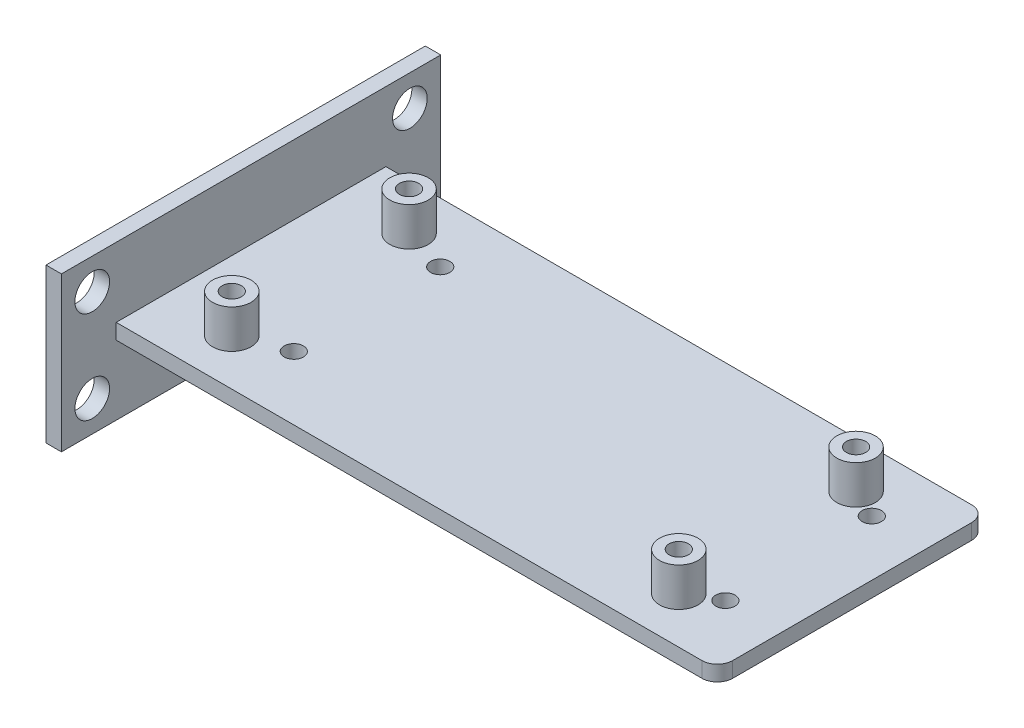
SolidWorks part; units mm, degrees
material "ABS"
ref_plane "Спереди" through (0, 0, 0) normal (0, 0, 1) x (1, 0, 0)
ref_plane "Сверху" through (0, 0, 0) normal (0, 1, 0) x (1, 0, 0)
ref_plane "Справа" through (0, 0, 0) normal (1, 0, 0) x (0, 0, -1)
sketch "Эскиз1" plane through (0, 0, 0) normal (0, 1, 0) x (1, 0, 0)
  line L1 (0, 0) -> (80, 0)
  line L2 (0, 0) -> (0, -35)
  line L3 (0, -35) -> (80, -35)
  line L4 (80, 0) -> (80, -35)
  dimension "D1" = 80
  dimension "D2" = 35
extrude "Бобышка-Вытянуть1" add sketch "Эскиз1" along normal blind 2
sketch "Эскиз2" plane through (0, 2, 0) normal (0, 1, 0) x (1, 0, 0)
  line L0 (0, 0) -> (0, -35) construction
  line L1 (80, -35) -> (80, 0) construction
  line L2 (80, 0) -> (0, 0) construction
  line L3 (0, -35) -> (80, -35) construction
  circle A0 centre (11, -6) radius 2.5
  circle A1 centre (11, -29) radius 2.5
  circle A2 centre (69, -6) radius 2.5
  circle A3 centre (69, -29) radius 2.5
  dimension "D1" = 11
  dimension "D2" = 11
  dimension "D3" = 11
  dimension "D4" = 11
  dimension "D5" = 6
  dimension "D6" = 6
  dimension "D7" = 5
  dimension "D8" = 6
  dimension "D9" = 6
  dimension "D10" = 5
  dimension "D11" = 5
  dimension "D12" = 5
extrude "Бобышка-Вытянуть2" add sketch "Эскиз2" along normal blind 5
sketch "Эскиз3" plane through (0, 7, 0) normal (0, 1, 0) x (1, 0, 0)
  circle A0 centre (11, -6) radius 1.25
  circle A1 centre (11, -29) radius 1.25
  circle A2 centre (69, -6) radius 1.25
  circle A3 centre (69, -29) radius 1.25
  dimension "D1" = 2.5
  dimension "D2" = 2.5
  dimension "D3" = 2.5
  dimension "D4" = 2.5
extrude "Вырез-Вытянуть1" cut sketch "Эскиз3" against normal through all both and the other way through all
sketch "Эскиз4" plane through (0, 2, 0) normal (0, 1, 0) x (1, 0, 0)
  line L0 (0, -17.5) -> (80, -17.5) construction
  line L1 (0, 0) -> (0, -35) construction
  line L2 (80, -35) -> (80, 0) construction
  circle A0 centre (4, -17.5) radius 2
  circle A1 centre (76, -17.5) radius 2
  dimension "D2" = 4
  dimension "D3" = 4
  dimension "D4" = 4
  dimension "D1" = 4
extrude "Вырез-Вытянуть2" [suppressed] cut sketch "Эскиз4" against normal through all
fillet "Скругление1" radius 2 1 edges at (0, 1, 0) type face fillet first side face at (0, 1, 17.5) second side face at (40, 1, 0)
fillet "Скругление2" radius 2 1 edges at (0, 1, 35) type face fillet first side face at (0, 1, 18.5) second side face at (40, 1, 35)
fillet "Скругление3" radius 2 1 edges at (80, 1, 35) type face fillet first side face at (41, 1, 35) second side face at (80, 1, 17.5)
fillet "Скругление4" radius 2 1 edges at (80, 1, 0) type face fillet first side face at (41, 1, 0) second side face at (80, 1, 16.5)
sketch "Эскиз5" plane through (0, 0, 0) normal (0, -1, 0) x (1, 0, 0)
  circle A0 centre (16.7893, 26.746) radius 1.25
  circle A1 centre (72.7893, 26.746) radius 1.25
  circle A2 centre (72.7893, 7.746) radius 1.25
  circle A3 centre (16.7893, 7.746) radius 1.25
  dimension "D1" = 2
  dimension "D2" = 2
extrude "Вырез-Вытянуть3" cut sketch "Эскиз5" against normal blind 10
sketch "Эскиз6" plane through (0, 0, 0) normal (0, -1, 0) x (1, 0, 0)
  circle A0 centre (16.7893, 26.746) radius 1.25
  circle A1 centre (16.7893, 26.746) radius 2.5
  circle A2 centre (72.7893, 26.746) radius 2.5
  circle A3 centre (72.7893, 26.746) radius 1.25
  circle A4 centre (72.7893, 7.746) radius 2.5
  circle A5 centre (72.7893, 7.746) radius 1.25
  circle A6 centre (16.7893, 7.746) radius 2.5
  circle A7 centre (16.7893, 7.746) radius 1.25
  dimension "D1" = 2
  dimension "D2" = 2
extrude "Бобышка-Вытянуть3" add sketch "Эскиз6" along normal blind 4
sketch "Эскиз7" plane through (0, 0, 0) normal (-1, 0, 0) x (0, 0, 1)
  line L0 (17.5, 2) -> (17.5, 0) construction
  line L1 (2, 2) -> (33, 2) construction
  line L2 (2, 0) -> (33, 0) construction
  line L3 (-7.1094, 1) -> (42.7824, 1) construction
  line L4 (42.1094, -9) -> (-7.1094, -9)
  line L5 (42.1094, -9) -> (42.1094, 11)
  line L6 (42.1094, 11) -> (-7.1094, 11)
  line L7 (-7.1094, -9) -> (-7.1094, 11)
  line L8 (42.1094, -9) -> (-7.1094, 11) construction
  line L9 (42.1094, 11) -> (-7.1094, -9) construction
  circle A0 centre (38.1094, -5) radius 2.25
  circle A1 centre (-3.1094, -5) radius 2.25
  circle A2 centre (-3.1094, 7) radius 2.25
  circle A3 centre (38.1094, 7) radius 2.25
  point P6 (17.5, 1)
  dimension "D1" = 4
  dimension "D2" = 4
  dimension "D3" = 20
extrude "Бобышка-Вытянуть4" add sketch "Эскиз7" against normal blind 2
